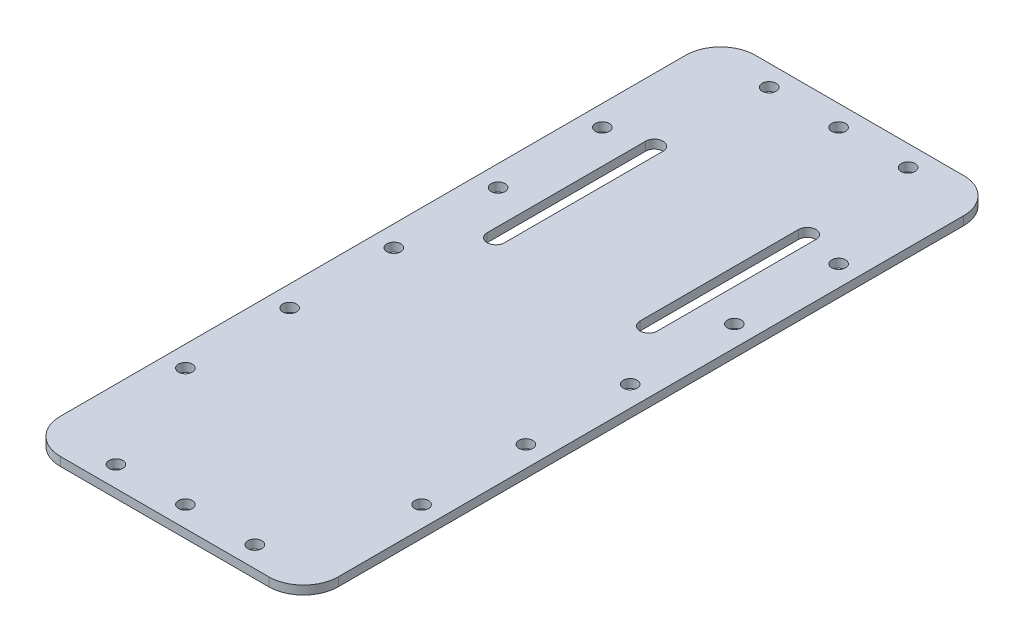
SolidWorks part; units mm, degrees
material "Thornel Mat VMA"
ref_plane "Front Plane" through (0, 0, 0) normal (0, 0, 1) x (1, 0, 0)
ref_plane "Top Plane" through (0, 0, 0) normal (0, 1, 0) x (1, 0, 0)
ref_plane "Right Plane" through (0, 0, 0) normal (1, 0, 0) x (0, 0, -1)
sketch "Sketch1" plane through (0, 0, 0) normal (0, 1, 0) x (1, 0, 0)
  line L0 (-157.6996, 42.9503) -> (197.9004, 42.9503) construction
  line L1 (-30.6996, 42.9503) -> (70.9004, 42.9503)
  line L2 (-30.6996, 42.9503) -> (-30.6996, -211.0497)
  line L3 (-30.6996, -211.0497) -> (70.9004, -211.0497)
  line L4 (70.9004, 42.9503) -> (70.9004, -211.0497)
  line L5 (-157.6996, -211.0497) -> (197.9004, -211.0497) construction
  dimension "D1" = 127
  dimension "D2" = 127
  dimension "D3" = 101.6
  dimension "D4" = 254
extrude "Boss-Extrude1" add sketch "Sketch1" along normal blind 3.175
sketch "Sketch2" plane through (0, 3.175, 0) normal (0, 1, 0) x (1, 0, 0)
  line L0 (20.1004, 42.9503) -> (20.1004, -50.0615) construction
  line L1 (70.9004, 42.9503) -> (-30.6996, 42.9503) construction
  line L2 (70.9004, -84.0497) -> (-81.795, -84.0497) construction
  line L3 (70.9004, -211.0497) -> (70.9004, 42.9503) construction
  line L4 (-30.6996, 42.9503) -> (-30.6996, -211.0497) construction
  circle A0 centre (-5.2996, 35.3303) radius 2.54
  circle A1 centre (20.1004, 35.3303) radius 2.54
  circle A2 centre (45.5004, 35.3303) radius 2.54
  circle A3 centre (-23.0796, -84.0497) radius 2.54
  circle A5 centre (-23.0796, -45.9497) radius 2.54
  circle A6 centre (-23.0796, -7.8497) radius 2.54
  circle A7 centre (63.2804, -7.8497) radius 2.54
  circle A8 centre (63.2804, -45.9497) radius 2.54
  circle A10 centre (63.2804, -84.0497) radius 2.54
  circle A12 centre (63.2804, -122.1497) radius 2.54
  circle A13 centre (63.2804, -160.2497) radius 2.54
  circle A14 centre (-23.0796, -160.2497) radius 2.54
  circle A15 centre (-23.0796, -122.1497) radius 2.54
  circle A17 centre (45.5004, -203.4297) radius 2.54
  circle A18 centre (20.1004, -203.4297) radius 2.54
  circle A19 centre (-5.2996, -203.4297) radius 2.54
  dimension "D3" = 5.08
  dimension "D4" = 5.08
  dimension "D5" = 5.08
  dimension "D10" = 5.08
  dimension "D11" = 5.08
  dimension "D12" = 5.08
  dimension "D1" = 25.4
  dimension "D2" = 25.4
  dimension "D6" = 38.1
  dimension "D8" = 38.1
  dimension "D13" = 7.62
  dimension "D14" = 7.62
extrude "Cut-Extrude1" cut sketch "Sketch2" against normal through all
fillet "Fillet1" radius 12.7 4 edges at (-30.6996, 1.5875, 211.0497) (70.9004, 1.5875, 211.0497) (70.9004, 1.5875, -42.9503) (-30.6996, 1.5875, -42.9503)
sketch "Sketch4" plane through (0, 0, 0) normal (0, 1, 0) x (1, 0, 0)
  line L0 (20.3128, 42.9503) -> (20.3128, -211.0497) construction
  line L1 (48.2528, -4.281) -> (48.2528, -62.2184) construction
  line L2 (51.4278, -4.281) -> (51.4278, -62.2184)
  line L3 (45.0778, -4.281) -> (45.0778, -62.2184)
  line L4 (-7.6272, -4.281) -> (-7.6272, -62.2184) construction
  line L5 (58.2004, 42.9503) -> (-17.9996, 42.9503) construction
  line L6 (-17.9996, -211.0497) -> (58.2004, -211.0497) construction
  line L7 (-10.8022, -4.281) -> (-10.8022, -62.2184)
  line L8 (-4.4522, -4.281) -> (-4.4522, -62.2184)
  arc A0 (51.4278, -4.281) -> (45.0778, -4.281) centre (48.2528, -4.281) ccw
  arc A1 (45.0778, -62.2184) -> (51.4278, -62.2184) centre (48.2528, -62.2184) ccw
  arc A2 (-10.8022, -4.281) -> (-4.4522, -4.281) centre (-7.6272, -4.281) cw
  arc A3 (-4.4522, -62.2184) -> (-10.8022, -62.2184) centre (-7.6272, -62.2184) cw
  point P4 (48.2528, -33.2497)
  point P15 (-7.6272, -33.2497)
  dimension "D1" = 27.94
  dimension "D2" = 76.2
  dimension "D3" = 6.35
extrude "Cut-Extrude7" cut sketch "Sketch4" along normal through all
